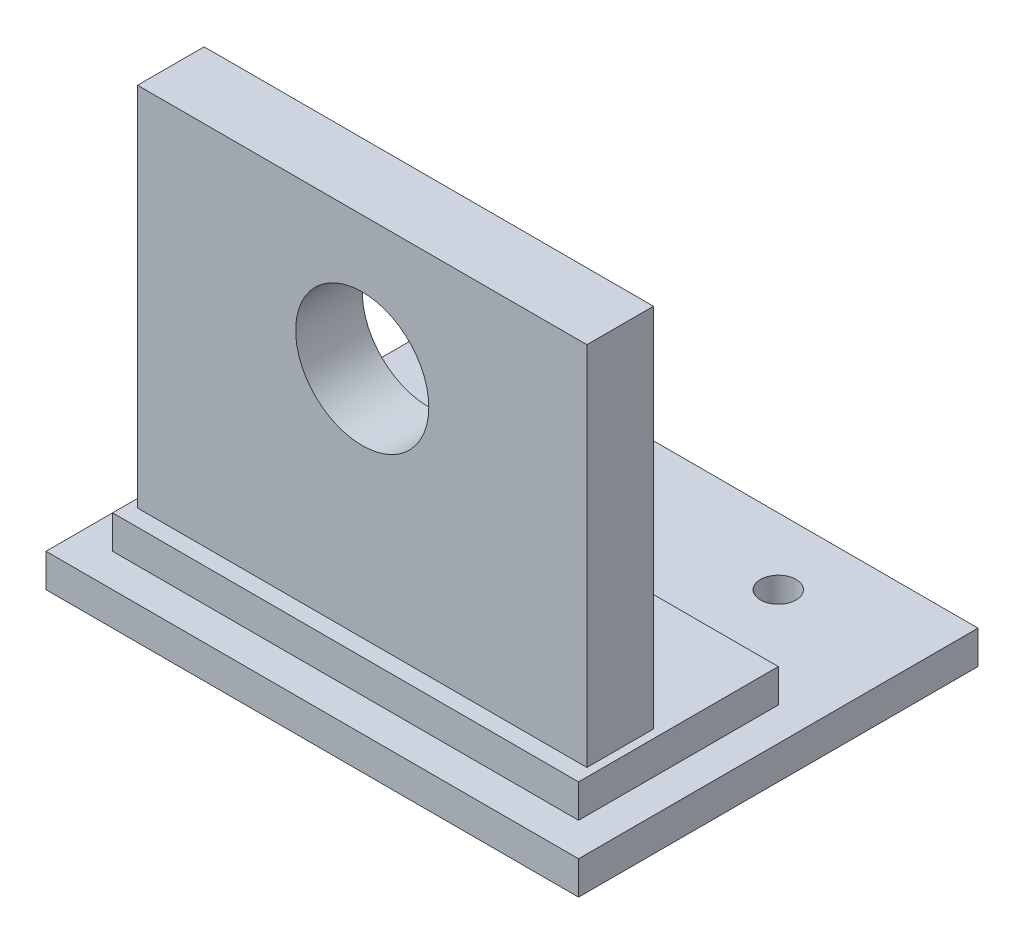
SolidWorks part; units mm, degrees
material "6061 Alloy"
ref_plane "Front Plane" through (0, 0, 0) normal (0, 0, 1) x (1, 0, 0)
ref_plane "Top Plane" through (0, 0, 0) normal (0, 1, 0) x (1, 0, 0)
ref_plane "Right Plane" through (0, 0, 0) normal (1, 0, 0) x (0, 0, -1)
sketch "Sketch2" plane through (0, 0, 0) normal (0, 1, 0) x (1, 0, 0)
  line L1 (-25.4, -12.7) -> (25.4, -12.7)
  line L2 (-25.4, -12.7) -> (-25.4, 12.7)
  line L4 (25.4, -12.7) -> (25.4, 12.7)
  line L5 (-25.4, -12.7) -> (25.4, 12.7) construction
  line L6 (-25.4, 12.7) -> (25.4, -12.7) construction
  line L8 (-25.4, 12.7) -> (-25.4, 25.4)
  line L9 (-25.4, 25.4) -> (25.4, 25.4)
  line L10 (25.4, 12.7) -> (25.4, 25.4)
  line L11 (0, 0) -> (0, 25.4) construction
  line L12 (-12.7, 19.05) -> (12.7, 19.05) construction
  point P0 (0, 0)
  point P6 (0, 19.05)
  point P14 (-12.7, 19.05)
  point P15 (12.7, 19.05)
  dimension "D1" = 50.8
  dimension "D2" = 25.4
  dimension "D3" = 12.7
  dimension "D4" = 25.4
  dimension "D5" = 6.35
extrude "Boss-Extrude1" add sketch "Sketch2" along normal blind 3.175
sketch "Sketch3" plane through (0, 3.175, 0) normal (0, 1, 0) x (1, 0, 0)
  line L0 (-25.4, -12.7) -> (25.4, -12.7) construction
  line L1 (-22.225, -9.525) -> (22.225, -9.525)
  line L2 (-22.225, -9.525) -> (-22.225, 9.525)
  line L3 (-22.225, 9.525) -> (22.225, 9.525)
  line L4 (22.225, -9.525) -> (22.225, 9.525)
  line L5 (-22.225, -9.525) -> (22.225, 9.525) construction
  line L6 (-22.225, 9.525) -> (22.225, -9.525) construction
  line L7 (-25.4, 25.4) -> (-25.4, -12.7) construction
  point P0 (0, 0)
  dimension "D2" = 3.175
  dimension "D1" = 3.175
extrude "Boss-Extrude2" add sketch "Sketch3" along normal blind 3.175
sketch "Sketch4" plane through (0, 6.35, 0) normal (0, 1, 0) x (1, 0, 0)
  line L0 (-22.225, -9.525) -> (22.225, -9.525) construction
  line L1 (-21.4313, -7.9375) -> (21.4313, -7.9375)
  line L2 (-21.4313, -7.9375) -> (-21.4313, -1.5875)
  line L3 (-21.4313, -1.5875) -> (21.4313, -1.5875)
  line L4 (21.4313, -7.9375) -> (21.4313, -1.5875)
  line L5 (-22.225, 9.525) -> (-22.225, -9.525) construction
  line L6 (0, 0) -> (0, -5.569) construction
  dimension "D1" = 1.5875
  dimension "D2" = 0.7937
  dimension "D3" = 6.35
extrude "Boss-Extrude3" add sketch "Sketch4" along normal blind 34.925
sketch "Sketch5" plane through (0, 0, 7.9375) normal (0, 0, 1) x (1, 0, 0)
  line L0 (0, 28.575) -> (0, 0) construction
  line L1 (-25.4, 3.175) -> (25.4, 3.175) construction
  circle A0 centre (0, 28.575) radius 6.35
  dimension "D2" = 12.7
  dimension "D1" = 25.4
extrude "Cut-Extrude1" cut sketch "Sketch5" against normal blind 34.925
hole_wizard "M3 Clearance Hole1" positions "3DSketch1" profile "Sketch6" hole size "M3" standard "ANSI Metric" end condition through all
sketch3d "3DSketch1"
  point P0 (-12.7, 0, -19.05)
  point P3 (12.7, 0, -19.05)
  point P7 (0, 0, 0)
sketch "Sketch6" plane through (-12.7, 0, -19.05) normal (1, 0, 0) x (0, 0, -1)
  line L0 (0, 0) -> (0, 41.275)
  line L1 (0, 41.275) -> (1.7, 41.275)
  line L2 (1.7, 41.275) -> (1.7, 0)
  line L5 (1.7, 0) -> (0, 0)
  line L11 (0, -6.35) -> (0, 107.95) construction
  dimension "Thru Hole Dia." = 3.4
  dimension "Thru Hole Depth" = 41.275
equation "\"D2@Sketch3\"=\"D1@Sketch3\""
